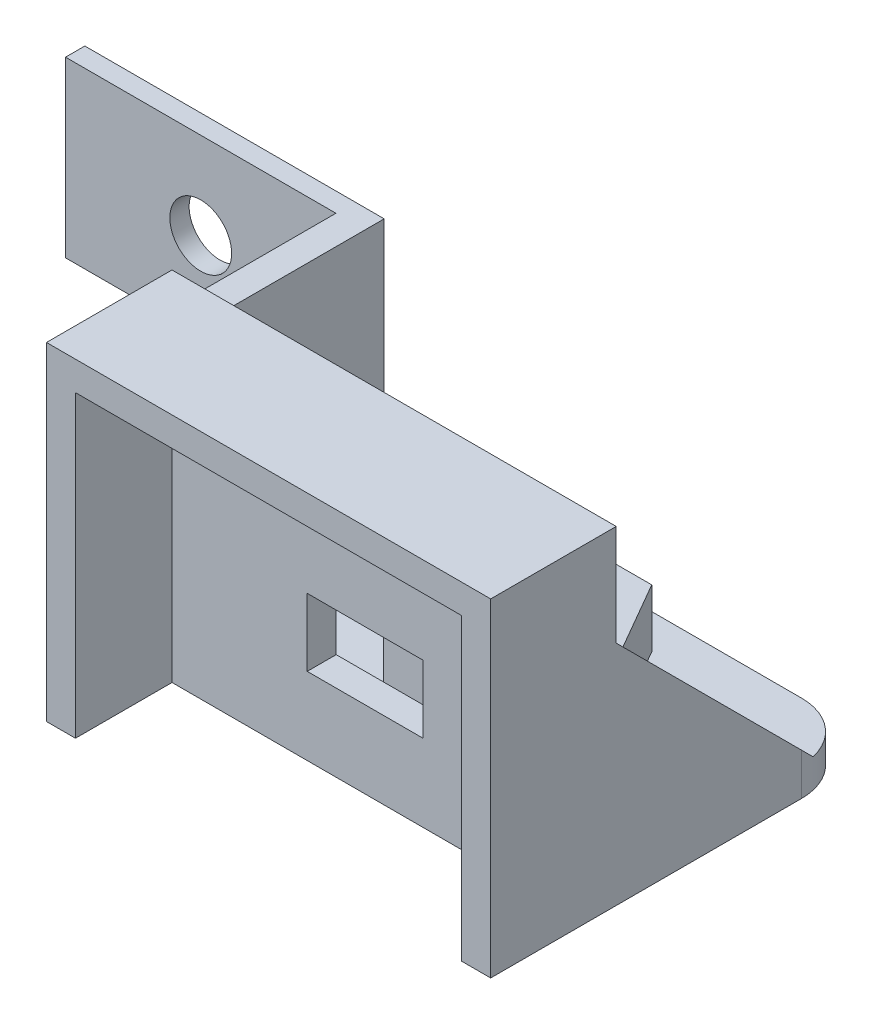
SolidWorks part; units mm, degrees
ref_plane "前视基准面" through (0, 0, 0) normal (0, 0, 1) x (1, 0, 0)
ref_plane "上视基准面" through (0, 0, 0) normal (0, 1, 0) x (1, 0, 0)
ref_plane "右视基准面" through (0, 0, 0) normal (1, 0, 0) x (0, 0, -1)
sketch "草图1" plane through (0, 0, 0) normal (0, 0, 1) x (1, 0, 0)
  line L1 (-11.5, 8.5) -> (11.5, 8.5)
  line L2 (-11.5, 8.5) -> (-11.5, -8.5)
  line L3 (-11.5, -8.5) -> (11.5, -8.5)
  line L4 (11.5, 8.5) -> (11.5, -8.5)
  line L5 (-11.5, 8.5) -> (11.5, -8.5) construction
  line L6 (-11.5, -8.5) -> (11.5, 8.5) construction
  point P0 (0, 0)
  dimension "D1" = 23
  dimension "D2" = 17
extrude "凸台-拉伸1" add sketch "草图1" along normal blind 6.5
sketch "草图2" plane through (0, 0, 6.5) normal (0, 0, 1) x (1, 0, 0)
  line L0 (0, -9.35) -> (0, 9.35) construction
  line L1 (-10, 7) -> (10, 7)
  line L2 (-10, 7) -> (-10, -8.5)
  line L3 (-10, -8.5) -> (10, -8.5)
  line L4 (10, 7) -> (10, -8.5)
  line L5 (-10, 7) -> (10, -8.5) construction
  line L6 (-10, -8.5) -> (10, 7) construction
  line L7 (-11.5, -8.5) -> (11.5, -8.5) construction
  line L8 (11.5, 8.5) -> (-11.5, 8.5) construction
  line L9 (-11.5, 8.5) -> (-11.5, -8.5) construction
  line L10 (11.5, -8.5) -> (11.5, 8.5) construction
  point P0 (0, -0.75)
  dimension "D1" = 1.5
  dimension "D2" = 1.5
  dimension "D3" = 1.5
extrude "切除-拉伸1" cut sketch "草图2" against normal blind 5
sketch "草图3" plane through (0, 0, 0) normal (0, 0, -1) x (-1, 0, 0)
  line L0 (-11.5, -8.5) -> (-11.5, 8.5) construction
  line L1 (-11.5, -7) -> (11.5, -7)
  line L2 (-11.5, -7) -> (-11.5, -8.5)
  line L3 (-11.5, -8.5) -> (11.5, -8.5)
  line L4 (11.5, -7) -> (11.5, -8.5)
  dimension "D1" = 1.5
extrude "凸台-拉伸2" add sketch "草图3" along normal blind 12.6
sketch "草图4" plane through (0, -7, 0) normal (0, 1, 0) x (1, 0, 0)
  line L0 (5.0807, 6.4) -> (2.5403, 10.8)
  line L1 (3.3486, 6.4) -> (1.6743, 9.3)
  line L2 (1.6743, 9.3) -> (-1.6743, 9.3)
  line L3 (-1.6743, 9.3) -> (-3.3486, 6.4)
  line L4 (-3.3486, 6.4) -> (-1.6743, 3.5)
  line L5 (-1.6743, 3.5) -> (1.6743, 3.5)
  line L6 (1.6743, 3.5) -> (3.3486, 6.4)
  line L7 (2.5403, 10.8) -> (-2.5403, 10.8)
  line L8 (-2.5403, 10.8) -> (-5.0807, 6.4)
  line L9 (-5.0807, 6.4) -> (-2.5403, 2)
  line L10 (-2.5403, 2) -> (2.5403, 2)
  line L11 (2.5403, 2) -> (5.0807, 6.4)
  line L12 (0, -9.35) -> (0, 9.35) construction
  line L13 (-11.5, 0) -> (11.5, 0) construction
  line L14 (-11.5, 12.6) -> (11.5, 12.6) construction
  circle A0 centre (0, 6.4) radius 2.9 construction
  dimension "D1" = 5.8
  dimension "D3" = 2
  dimension "D4" = 1.8
  dimension "D2" = 1.5
extrude "凸台-拉伸3" add sketch "草图4" along normal blind 3
hole_wizard "M3 间隙孔1" positions "草图8" profile "草图9" hole size "M3" standard "ISO" end condition up to next
sketch "草图8" plane through (0, -7, 0) normal (0, 1, 0) x (1, 0, 0)
  point P0 (0, 6.4)
  point P5 (0, 0)
sketch "草图9" plane through (0, -7, -6.4) normal (1, 0, 0) x (0, 0, 1)
  line L0 (0, 0) -> (0, 1.5)
  line L1 (0, 1.5) -> (1.6, 1.5)
  line L2 (1.6, 1.5) -> (1.6, 0)
  line L5 (1.6, 0) -> (0, 0)
  line L11 (0, -6.35) -> (0, 107.95) construction
  dimension "通孔孔直径" = 3.2
  dimension "通孔孔深度" = 1.5
ref_plane "基准面4" through (0, -3.5, -3.5) normal (0, -0.7071, -0.7071) x (-1, 0, 0)
sketch "草图7" plane through (0, -3.5, -3.5) normal (0, -0.7071, -0.7071) x (-1, 0, 0)
  line L0 (-11.5, -10.6066) -> (-11.5, 2.8991) construction
  line L1 (-10, -4.9497) -> (-11.5, -4.9497)
  line L2 (-10, -4.9497) -> (-10, 2.3101)
  line L3 (-10, 2.3101) -> (-11.5, 2.3101)
  line L4 (-11.5, -4.9497) -> (-11.5, 2.3101)
  line L5 (11.5, -4.9497) -> (-11.5, -4.9497) construction
  dimension "D1" = 1.5
extrude "凸台-拉伸6" add sketch "草图7" along normal up to surface and the other way up to surface up to face at (0, -7, -6.3) other way up to face at (0, 0.75, 0)
fillet "圆角1" radius 3 2 edges at (-11.5, -7.75, -12.6) (11.5, -7.75, -12.6)
sketch "草图10" plane through (0, 0, 0) normal (0, 0, -1) x (-1, 0, 0)
  line L0 (11.5, 8.5) -> (11.5, -7) construction
  line L1 (11.5, 6.8) -> (10, 6.8)
  line L2 (11.5, 6.8) -> (11.5, -2.2)
  line L3 (11.5, -2.2) -> (10, -2.2)
  line L4 (10, 6.8) -> (10, -2.2)
  line L5 (25.5, -2.2) -> (11.5, -2.2) construction
  dimension "D1" = 1.5
  dimension "D2" = 9
extrude "凸台-拉伸7" add sketch "草图10" along normal up to surface (9.4863 mm away) up to face at (0, -0.375, 6.5)
sketch "草图11" plane through (-11.5, 0, 0) normal (-1, 0, 0) x (0, 0, 1)
  line L0 (-9.4863, -2.2) -> (0, -2.2) construction
  line L1 (-9.4863, 6.8) -> (-8.4863, 6.8)
  line L2 (-9.4863, 6.8) -> (-9.4863, -2.2)
  line L3 (-9.4863, -2.2) -> (-8.4863, -2.2)
  line L4 (-8.4863, 6.8) -> (-8.4863, -2.2)
  dimension "D1" = 1
extrude "凸台-拉伸8" add sketch "草图11" along normal up to surface (14 mm away) up to face at (0, -8.5, -4.8)
hole_wizard "M3 间隙孔2" positions "草图12" profile "草图13" hole size "M3" standard "ISO" end condition up to next
sketch "草图12" plane through (0, 0, -8.4863) normal (0, 0, 1) x (1, 0, 0)
  point P0 (-18.5, 2.3)
sketch "草图13" plane through (-18.5, 2.3, -8.4863) normal (1, 0, 0) x (0, -1, 0)
  line L0 (0, 0) -> (0, 1)
  line L1 (0, 1) -> (1.6, 1)
  line L2 (1.6, 1) -> (1.6, 0)
  line L5 (1.6, 0) -> (0, 0)
  line L11 (0, -6.35) -> (0, 107.95) construction
  dimension "通孔孔直径" = 3.2
  dimension "通孔孔深度" = 1
sketch "草图14" plane through (0, 0, 0) normal (0, 0, -1) x (-1, 0, 0)
  line L1 (3, -1) -> (-3, -1)
  line L2 (3, -1) -> (3, -4.5)
  line L3 (3, -4.5) -> (-3, -4.5)
  line L4 (-3, -1) -> (-3, -4.5)
extrude "切除-拉伸2" cut sketch "草图14" against normal up to next
